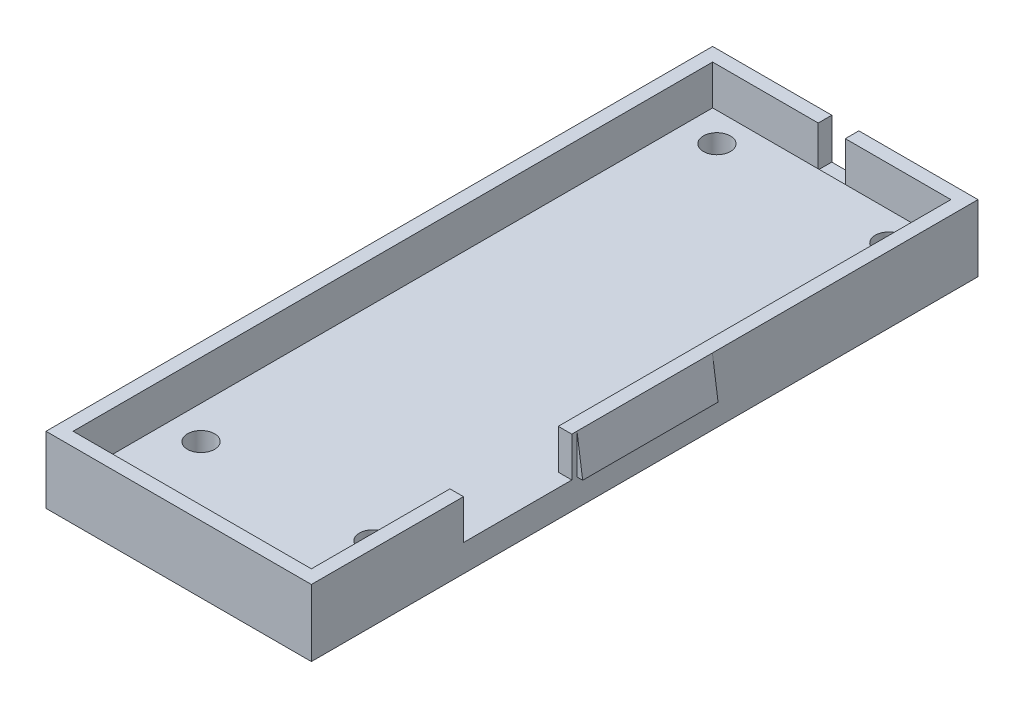
SolidWorks part; units mm, degrees
ref_plane "Front Plane" through (0, 0, 0) normal (0, 0, 1) x (1, 0, 0)
ref_plane "Top Plane" through (0, 0, 0) normal (0, 1, 0) x (1, 0, 0)
ref_plane "Right Plane" through (0, 0, 0) normal (1, 0, 0) x (0, 0, -1)
sketch "Sketch1" plane through (0, 0, 0) normal (0, 1, 0) x (1, 0, 0)
  line L0 (14.7, -36.925) -> (14.7, 36.925)
  line L1 (12.7, -34.925) -> (-12.7, -34.925)
  line L2 (12.7, -34.925) -> (12.7, 34.925)
  line L3 (12.7, 34.925) -> (-12.7, 34.925)
  line L4 (-12.7, -34.925) -> (-12.7, 34.925)
  line L5 (12.7, -34.925) -> (-12.7, 34.925) construction
  line L6 (12.7, 34.925) -> (-12.7, -34.925) construction
  line L7 (14.7, 36.925) -> (-14.7, 36.925)
  line L8 (-14.7, -36.925) -> (-14.7, 36.925)
  line L9 (14.7, -36.925) -> (-14.7, -36.925)
  line L10 (13.2, -35.425) -> (13.2, 35.425)
  line L11 (13.2, 35.425) -> (-13.2, 35.425)
  line L12 (-13.2, -35.425) -> (-13.2, 35.425)
  line L13 (13.2, -35.425) -> (-13.2, -35.425)
  point P0 (0, 0)
  dimension "D1" = 25.4
  dimension "D2" = 69.85
  dimension "D3" = 2
  dimension "D4" = 0.5
extrude "Boss-Extrude1" add sketch "Sketch1" against normal blind 3 contours L4 L1 L2 L3 | L13 L10 L11 L12 L1 L4 L3 L2 | L9 L0 L7 L8 L10 L13 L12 L11 region at (0, 0, 36.1301) region at (0, 0, 0) region at (0, 0, 35.3494)
extrude "Boss-Extrude2" add sketch "Sketch1<3>" along normal blind 4.4 contours L9 L0 L7 L8 L10 L13 L12 L11 region at (0, 0, 36.1301)
sketch "Sketch1<3>" plane through (0, 0, 0) normal (0, 1, 0) x (1, 0, 0) same geometry as "Sketch1"
sketch "Sketch2" plane through (0, 0, 0) normal (0, 1, 0) x (1, 0, 0)
  line L0 (-12.7, -34.925) -> (-12.7, 34.925) construction
  line L1 (-9.525, 32.225) -> (9.525, 32.225)
  line L2 (-9.525, 32.225) -> (-9.525, -24.925)
  line L3 (-9.525, -24.925) -> (9.525, -24.925)
  line L4 (9.525, 32.225) -> (9.525, -24.925)
  line L5 (12.7, -34.925) -> (12.7, 34.925) construction
  line L6 (12.7, 34.925) -> (-12.7, 34.925) construction
  circle A0 centre (-9.525, 32.225) radius 1.5
  circle A1 centre (9.525, 32.225) radius 1.5
  circle A2 centre (9.525, -24.925) radius 1.5
  circle A3 centre (-9.525, -24.925) radius 1.5
  dimension "D5" = 3
  dimension "D1" = 3.175
  dimension "D2" = 3.175
  dimension "D3" = 2.7
  dimension "D4" = 57.15
extrude "Cut-Extrude1" cut sketch "Sketch2" against normal through all both and the other way through all contours L4 A1 L1 | L1 A1 L4 | A0 | A3 | A2 region at (9.7372, 0, -32.4372) region at (8.8884, 0, -31.5884)
sketch "Sketch3" plane through (0, 0, -36.925) normal (0, 0, -1) x (-1, 0, 0)
  line L0 (0, 0) -> (0, 4.4) construction
  line L1 (-14.7, 4.4) -> (14.7, 4.4) construction
  line L3 (1.5, 4.4) -> (-1.5, 4.4)
  line L4 (1.5, 4.4) -> (1.5, -0.1)
  line L5 (1.5, -0.1) -> (-1.5, -0.1)
  line L6 (-1.5, 4.4) -> (-1.5, -0.1)
  line L7 (1.5, 4.4) -> (-1.5, -0.1) construction
  line L8 (1.5, -0.1) -> (-1.5, 4.4) construction
  point P5 (0, 2.15)
  dimension "D1" = 3
  dimension "D2" = 4.5
extrude "Cut-Extrude2" cut sketch "Sketch3" against normal up to surface (1.5 mm away) up to face at (0, 2.2, -35.425)
sketch "Sketch4" plane through (13.2, 0, 0) normal (-1, 0, 0) x (0, 0, 1)
  line L0 (36.925, 4.4) -> (-36.925, 4.4) construction
  line L1 (8.075, 0) -> (20.075, 0)
  line L2 (8.075, 0) -> (8.075, 4.4)
  line L3 (8.075, 4.4) -> (20.075, 4.4)
  line L4 (20.075, 0) -> (20.075, 4.4)
  line L5 (-36.925, -3) -> (-36.925, 4.4) construction
  line L6 (0, 0) -> (8.075, 0) construction
  dimension "D1" = 45
  dimension "D2" = 12
extrude "Cut-Extrude3" cut sketch "Sketch4" against normal up to surface (1.5 mm away) up to face at (14.7, 0.7, 0)
sketch "Sketch5" plane through (-14.7, 0, 0) normal (-1, 0, 0) x (0, 0, 1)
  line L0 (36.925, 4.4) -> (-36.925, 4.4) construction
  line L1 (-7.5, 4.4) -> (7.5, 4.4)
  line L2 (-7.5, 4.4) -> (-7.5, 0)
  line L3 (-7.5, 0) -> (7.5, 0)
  line L4 (7.5, 4.4) -> (7.5, 0)
  line L5 (0, 4.4) -> (0, 0) construction
  point P9 (0, 0)
  dimension "D1" = 15
extrude "Boss-Extrude3" add sketch "Sketch5" along normal blind 1
chamfer "Chamfer1" distance 1 distance2 7 1 edges at (-15.7, 4.4, 0) first distance on face at (-4.5571, 4.4, 2.8679)
mirror "Mirror1" about plane through (0, 0, 0) normal (1, 0, 0) of "Boss-Extrude3"
chamfer "Chamfer2" distance 7 distance2 1 1 edges at (15.7, 4.4, 0) first distance on face at (15.7, 2.2, 0)
